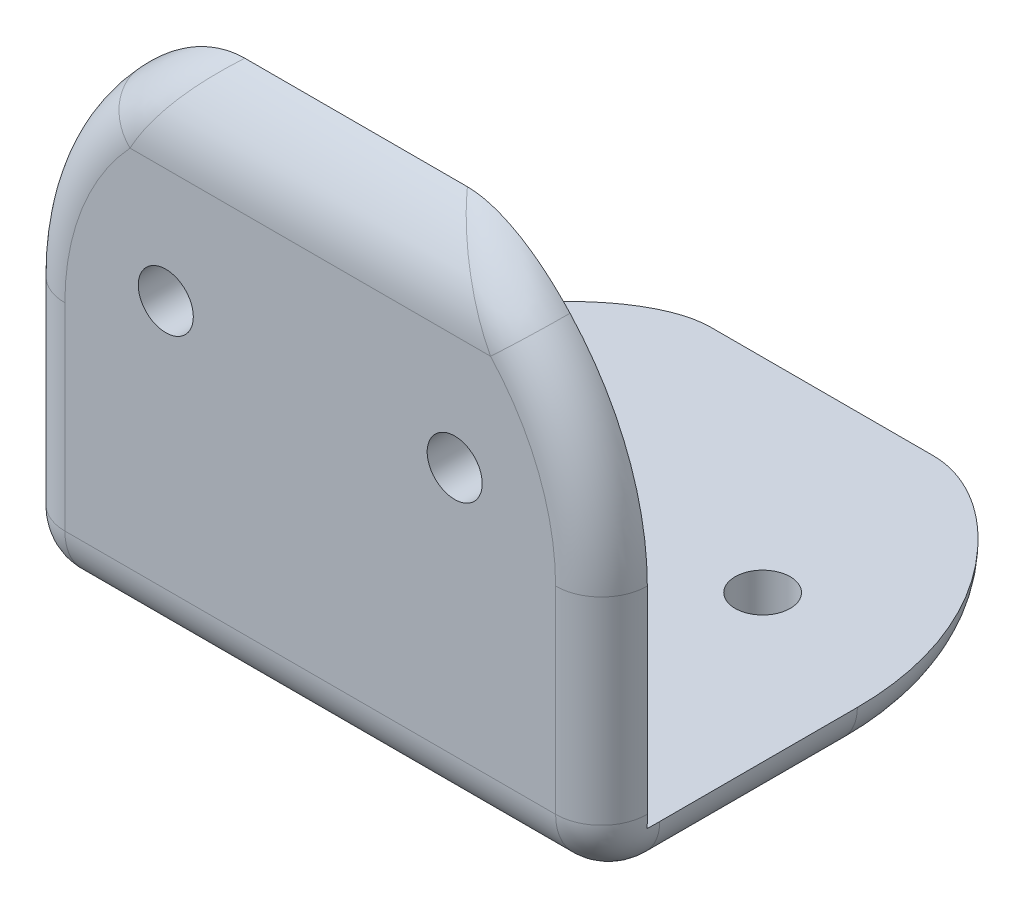
SolidWorks part; units mm, degrees
ref_plane "Front Plane" through (0, 0, 0) normal (0, 0, 1) x (1, 0, 0)
ref_plane "Top Plane" through (0, 0, 0) normal (0, 1, 0) x (1, 0, 0)
ref_plane "Right Plane" through (0, 0, 0) normal (1, 0, 0) x (0, 0, -1)
sketch "Sketch1" plane through (0, 0, 0) normal (1, 0, 0) x (0, 0, -1)
  line L0 (-2.5, 25.4) -> (-2.5, -2.5)
  line L1 (-2.5, -2.5) -> (25.4, -2.5)
  line L2 (25.4, -2.5) -> (25.4, 0)
  line L3 (25.4, 0) -> (0, 0)
  line L4 (0, 0) -> (0, 25.4)
  line L5 (0, 25.4) -> (-2.5, 25.4)
  dimension "D1" = 2.5
  dimension "D2" = 2.5
  dimension "D3" = 25.4
  dimension "D4" = 25.4
extrude "Boss-Extrude1" add sketch "Sketch1" along normal blind 31.75
fillet "Fillet1" radius 6 2 edges at (15.875, 25.4, 2.5) (15.875, -2.5, -25.4)
sketch "Sketch2" plane through (0, 0, 2.5) normal (0, 0, 1) x (1, 0, 0)
  line L0 (8.001, 14.2875) -> (23.749, 14.2875) construction
  line L1 (31.75, -2.5) -> (0, -2.5) construction
  line L2 (31.75, 20.5266) -> (31.75, -2.5) construction
  line L3 (15.875, 25.4) -> (15.875, -2.5) construction
  line L4 (0, 20.5266) -> (0, -2.5) construction
  line L5 (31.75, 25.4) -> (0, 25.4) construction
  line L7 (0, 11.45) -> (0, 25.4)
  line L8 (0, 25.4) -> (31.75, 25.4)
  line L9 (31.75, 25.4) -> (31.75, 11.45)
  circle A0 centre (8.001, 14.2875) radius 1.5
  circle A1 centre (23.749, 14.2875) radius 1.5
  arc A2 (31.75, 11.45) -> (0, 11.45) centre (15.875, 11.45) ccw
  point P4 (15.875, 14.2875)
  point P7 (15.875, -2.5)
  point P9 (15.875, 11.45)
  line M3 (31.75, -2.5) -> (31.75, 20.5266)
  line M4 (31.75, 20.5266) -> (0, 20.5266)
  line M5 (0, 20.5266) -> (0, -2.5)
  dimension "D1" = 3
  dimension "D2" = 15.748
  dimension "D3" = 14.2875
extrude "Cut-Extrude1" cut sketch "Sketch2" against normal through all contours A0 | A1 | A2 L9 L8 M4 | A2 M3 M4 | A2 L8 L7 M4 | A2 M4 M5 | L8 A2 region at (0.8402, 18.3002, 2.5) region at (2.8053, 23.3825, 2.5) region at (15.875, 26.1741, 2.5) region at (30.9098, 18.3002, 2.5) region at (28.9447, 23.3825, 2.5) region at (8.001, 14.2875, 2.5) region at (23.749, 14.2875, 2.5)
sketch "Sketch3" plane through (0, -2.5, 0) normal (0, -1, 0) x (1, 0, 0)
  line L0 (8.001, -14.2875) -> (23.749, -14.2875) construction
  line L1 (31.75, 2.5) -> (0, 2.5) construction
  line L2 (15.875, -25.4) -> (15.875, 2.5) construction
  line L4 (31.75, -25.4) -> (0, -25.4) construction
  line L5 (31.75, 2.5) -> (31.75, -20.5266) construction
  line L6 (31.75, -25.4) -> (31.75, -11.45)
  line L7 (31.75, -25.4) -> (0, -25.4)
  line L8 (0, -25.4) -> (0, -11.45)
  circle A0 centre (8.001, -14.2875) radius 1.5
  circle A1 centre (23.749, -14.2875) radius 1.5
  arc A2 (0, -11.45) -> (31.75, -11.45) centre (15.875, -11.45) ccw
  point P4 (15.875, -14.2875)
  point P18 (15.875, 2.5)
  line M3 (0, 2.5) -> (0, -20.5266)
  line M4 (0, -20.5266) -> (31.75, -20.5266)
  line M5 (31.75, -20.5266) -> (31.75, 2.5)
  dimension "D1" = 3
  dimension "D2" = 15.748
  dimension "D3" = 14.2875
extrude "Cut-Extrude2" cut sketch "Sketch3" against normal through all contours A2 M4 M5 | A2 M3 M4 | A1 | A0 | A2 L8 L7 M4 | A2 L7 L6 M4 region at (28.9447, -2.5, -23.3825) region at (30.9098, -2.5, -18.3002) region at (2.8053, -2.5, -23.3825) region at (0.8402, -2.5, -18.3002) region at (8.001, -2.5, -14.2875) region at (23.749, -2.5, -14.2875)
fillet "Fillet2" radius 3.175 1 edges at (15.875, -2.5, 2.5)
fillet "Fillet3" radius 2.5 12 edges at (31.0206, -2.5, -16.2069) (31.75, -2.5, -6.0625) (31.75, -1.5701, 1.5701) (31.75, 6.0625, 2.5) (31.0206, 16.2069, 2.5) (0.7294, 16.2069, 2.5) (0, 6.0625, 2.5) (0, -1.5701, 1.5701) (0, -2.5, -6.0625) (0.7294, -2.5, -16.2069) (26.9493, 22.8243, 2.0426) (4.8007, -2.0426, -22.8243)
sketch "Sketch4" plane through (0, -2.5, 0) normal (0, -1, 0) x (1, 0, 0)
  line L5 (0, -6.35) -> (31.75, -6.35)
  line L6 (0, -11.45) -> (0, -0.675) construction
  line L7 (31.75, -11.45) -> (31.75, -0.675) construction
  line L8 (31.75, -6.35) -> (31.75, -25.4)
  line L9 (31.75, -25.4) -> (0, -25.4)
  line L10 (0, -25.4) -> (0, -6.35)
  line L11 (31.7343, 0) -> (0.0157, 0) construction
  spline S0 degree 3 poles (27.535, -22.2232) (27.1608, -22.6281) (26.7689, -23.0115) (25.942, -23.7264) (25.5071, -24.0577) (24.8084, -24.4988) (24.567, -24.6366) (24.0747, -24.884) (23.823, -24.9942) (23.3059, -25.1816) (23.0386, -25.2592) (22.4957, -25.3683) (22.2213, -25.4) (21.9428, -25.4) knots 0 0 0 0 0.25 0.25 0.5 0.5 0.625 0.625 0.75 0.75 0.875 0.875 1 1 1 1 construction
  dimension "D1" = 6.35
extrude "Cut-Extrude3" [suppressed] cut sketch "Sketch4" against normal through all
